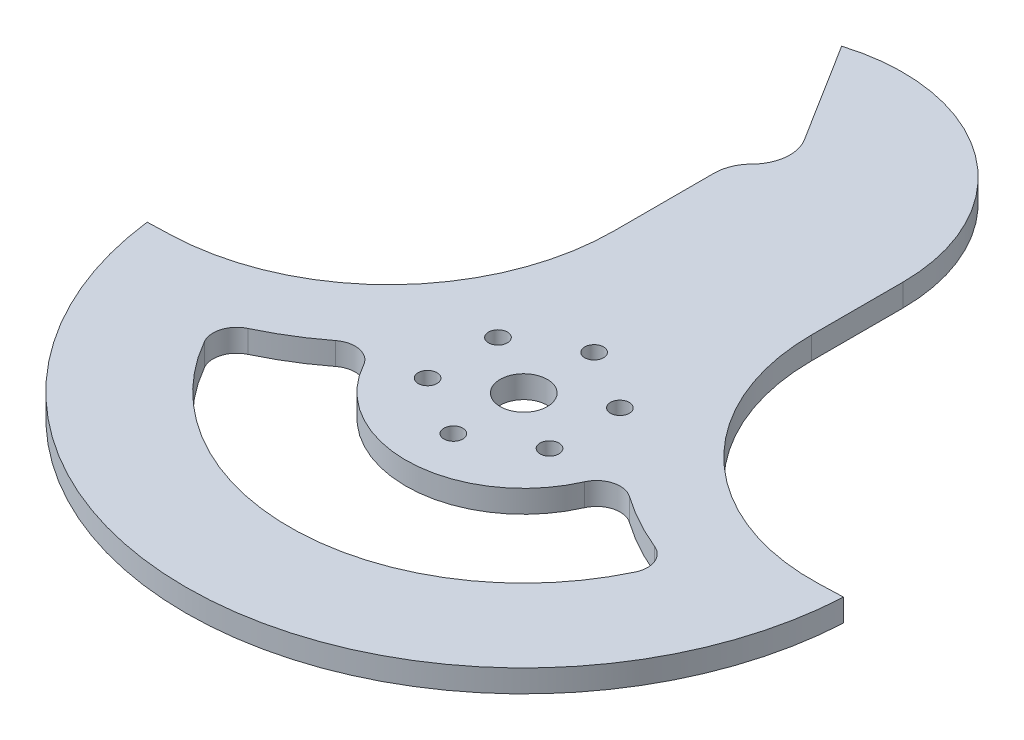
SolidWorks part; units mm, degrees
ref_plane "Front Plane" through (0, 0, 0) normal (0, 0, 1) x (1, 0, 0)
ref_plane "Top Plane" through (0, 0, 0) normal (0, 1, 0) x (1, 0, 0)
ref_plane "Right Plane" through (0, 0, 0) normal (1, 0, 0) x (0, 0, -1)
other "Center of Mass"
sketch "Sketch1" plane through (0, 0, 0) normal (0, 1, 0) x (1, 0, 0)
  line L0 (0, 0) -> (-23040.0357, 36803.9862) construction
  line L1 (0, -1000) -> (0, 49000) construction
  line L2 (-29.7853, 97.136) -> (-16.5198, 75.9457)
  line L3 (18.7342, 112.0138) -> (41531.855, 12841.4067) construction
  line L4 (-20, 60.3286) -> (20, 60.3286) construction
  line L5 (-20, 60.3286) -> (-20, 39.1549)
  line L6 (20, 60.3286) -> (20, 40.9875)
  line L7 (0, 0) -> (-71.0663, -8.7258) construction
  line L8 (0, 0) -> (71.5019, -3.7473) construction
  line L9 (-71.0663, -8.7258) -> (71.5019, -3.7473) construction
  line L10 (-71.0663, -8.7258) -> (-66.0694, -8.5513)
  line L11 (71.5019, -3.7473) -> (66.5049, -3.9218)
  line L12 (-28.8426, 54.8122) -> (35326.4965, 35410.1512) construction
  circle A0 centre (0, 0) radius 101.6 construction
  arc A1 (-16.5198, 75.9457) -> (-17.6481, 66.0067) centre (-23.3262, 71.6848) cw
  arc A2 (-17.6481, 66.0067) -> (-20, 60.3286) centre (-11.97, 60.3286) ccw
  arc A3 (-29.7853, 97.136) -> (20, 60.3286) centre (-18.4989, 60.3286) cw
  circle A4 centre (0, 0) radius 71.6 construction
  arc A5 (-71.0663, -8.7258) -> (71.5019, -3.7473) centre (0, 0) ccw
  arc A6 (-66.0694, -8.5513) -> (-20, 39.1549) centre (-67.7353, 39.1549) ccw
  arc A7 (20, 40.9875) -> (66.5049, -3.9218) centre (64.9367, 40.9875) ccw
  circle A8 centre (0, 0) radius 30.5026 construction
  point P9 (0, 60.3286)
  point P20 (0, -71.6)
  point P21 (0, -101.6)
  point P31 (2.4988, -71.5564)
  point P32 (0, 0)
  point P34 (-15.2961, 71.6848)
  point P36 (0, 0)
  point P37 (0, 0)
  point P38 (0, 0)
  dimension "D1" = 203.2
  dimension "D2" = 75
  dimension "D3" = 25
  dimension "D4" = 40
  dimension "D5" = 30
  dimension "D6" = 92
  dimension "D7" = 170
  dimension "D8" = 5
  dimension "D9" = 45
extrude "Boss-Extrude1" add sketch "Sketch1" along normal blind 4.7625
sketch "Sketch6" plane through (0, 4.7625, 0) normal (0, 1, 0) x (1, 0, 0)
  line L0 (-41.0794, -17.6358) -> (-47.4528, -4.0572) construction
  line L1 (29.2213, -7.1458) -> (38.1596, 4.9002) construction
  arc A0 (-45.5884, -19.5412) -> (46.8909, -16.168) centre (0, 0) ccw
  arc A1 (-16.623, 2.7783) -> (-45.5884, -19.5412) centre (-67.7353, 39.1549) cw
  arc A2 (14.252, 8.9958) -> (46.8909, -16.168) centre (64.9367, 40.9875) ccw
  arc A3 (-16.623, 2.7783) -> (14.252, 8.9958) centre (0, 0) ccw
  arc A4 (-66.0694, -8.5513) -> (-20, 39.1549) centre (-67.7353, 39.1549) ccw construction
  arc A5 (-71.0663, -8.7258) -> (71.5019, -3.7473) centre (0, 0) ccw construction
  arc A6 (20, 40.9875) -> (66.5049, -3.9218) centre (64.9367, 40.9875) ccw construction
  circle A7 centre (0, 0) radius 30.5026 construction
  point P23 (0, -49.6)
  point P24 (27.5979, 7.7355)
  point P26 (-27.0864, -6.2166)
  point P27 (23.3858, 11.7369)
  dimension "D1" = 22
  dimension "D2" = 15
extrude "Cut-Extrude2" cut sketch "Sketch6" against normal through all
fillet "Fillet6" radius 5 2 edges at (46.8909, 2.3813, 16.168) (-45.5884, 2.3813, 19.5412)
sketch "Sketch7" plane through (0, 4.7625, 0) normal (0, 1, 0) x (1, 0, 0)
  circle A0 centre (0, 0) radius 25
  point P3 (0, 0)
  dimension "D1" = 50
extrude "Boss-Extrude5" add sketch "Sketch7" against normal up to surface (4.7625 mm away) up to face at (0.9289, 0, 19.6333)
fillet "Fillet7" radius 5 2 edges at (24.7558, 2.3813, 3.486) (-24.2527, 2.3813, 6.0666)
sketch "Sketch8" plane through (0, 4.7625, 0) normal (0, 1, 0) x (1, 0, 0)
  circle A0 centre (0.1682, -0.1726) radius 5
  point P2 (1.1861, -0.8784)
  point P3 (0.208, -0.178)
  point P4 (0.1725, -0.2345)
  point P5 (0, 0)
  point P6 (0.1672, -0.1743)
  point P7 (0.1681, -0.1726)
  point P8 (0.1682, -0.1726)
  point P9 (0, 0)
  point P10 (0, 0)
  dimension "D1" = 10
extrude "Cut-Extrude3" cut sketch "Sketch8" against normal through all
sketch "Sketch10" plane through (0, 4.7625, 0) normal (0, 1, 0) x (1, 0, 0)
  circle A0 centre (0.1682, -15.0858) radius 9.9133 construction
  circle A1 centre (0, 0) radius 25 construction
  circle A2 centre (0.1682, -0.1726) radius 5 construction
  circle A3 centre (0.1682, -15.0858) radius 2
  circle A4 centre (-12.7471, -7.6292) radius 2
  circle A5 centre (-12.7471, 7.2841) radius 2
  circle A6 centre (0.1682, 14.7407) radius 2
  circle A7 centre (13.0834, 7.2841) radius 2
  circle A8 centre (13.0834, -7.6292) radius 2
  point P7 (14.4943, 6.8619)
  point P9 (0, 0)
  point P21 (0.1682, -0.1726)
  dimension "D1" = 4
  dimension "D2" = 6
extrude "Cut-Extrude4" cut sketch "Sketch10" against normal through all
sketch "Sketch11" plane through (0, 0, 0) normal (0, 1, 0) x (1, 0, 0)
  circle A0 centre (0.1682, -0.1726) radius 101.8143 construction
  circle A1 centre (0.1682, -0.1726) radius 5 construction
  circle A2 centre (0.1682, -0.1726) radius 71.7461 construction
